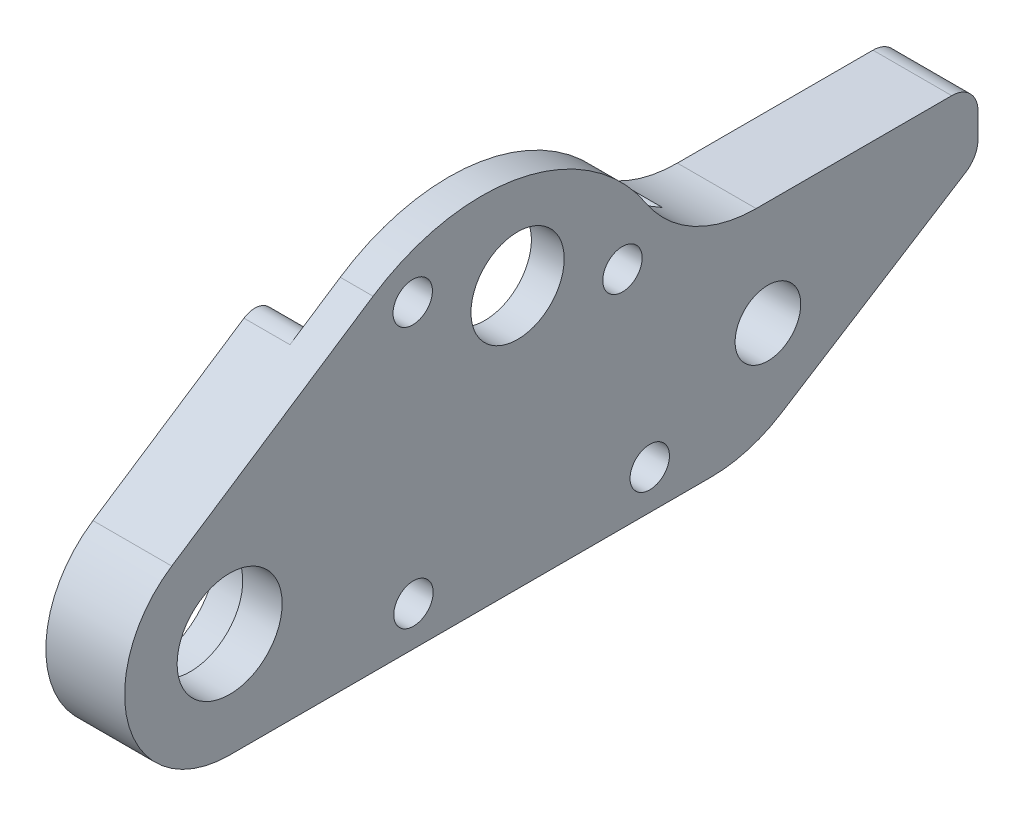
SolidWorks part; units mm, degrees
material "1060 Alloy"
ref_plane "Front Plane" through (0, 0, 0) normal (0, 0, 1) x (1, 0, 0)
ref_plane "Top Plane" through (0, 0, 0) normal (0, 1, 0) x (1, 0, 0)
ref_plane "Right Plane" through (0, 0, 0) normal (1, 0, 0) x (0, 0, -1)
sketch "Sketch27" plane through (0, 0, 0) normal (1, 0, 0) x (0, 0, -1)
  line L0 (4.5897, 48.6745) -> (19.925, 58.8075)
  line L1 (48.5644, 34) -> (66, 45)
  line L2 (66, 45) -> (66, 50)
  line L3 (38.9191, 51.0928) -> (22.9443, 56.9072) construction
  line L4 (66, 50) -> (49.1015, 50)
  line L6 (48.5644, 34) -> (9, 34)
  line L8 (0, 0) -> (60, 0) construction
  line L9 (0, 0) -> (0, 58) construction
  line L10 (0, 58) -> (60, 58) construction
  line L11 (60, 0) -> (60, 58) construction
  arc A0 (4.5897, 48.6745) -> (9, 34) centre (9, 42) ccw
  circle A1 centre (30.9317, 54) radius 12.5 construction
  arc A2 (40.7386, 54.5171) -> (19.925, 58.8075) centre (28.1943, 46.2928) ccw
  circle A3 centre (30.9317, 54) radius 3.55
  circle A4 centre (50, 42) radius 6 construction
  circle A5 centre (9, 42) radius 4
  circle A6 centre (50, 42) radius 2.5
  circle A7 centre (38.9191, 51.0928) radius 1.5
  circle A8 centre (22.9443, 56.9072) radius 1.5
  circle A9 centre (38.9191, 51.0928) radius 3.25 construction
  circle A10 centre (22.9443, 56.9072) radius 3.25 construction
  arc A12 (49.1015, 50) -> (40.7386, 54.5171) centre (49.1015, 60) cw
  dimension "D9" = 12
  dimension "D10" = 5
  dimension "D11" = 15
  dimension "D12" = 8
  dimension "D13" = 8
  dimension "D14" = 5
  dimension "D15" = 25
  dimension "D6" = 25
  dimension "D17" = 7.1
  dimension "D16" = 3
  dimension "D19" = 6.5
  dimension "D20" = 10
  dimension "D1" = 60
  dimension "D2" = 58
  dimension "D3" = 42
  dimension "D4" = 9
  dimension "D5" = 42
  dimension "D7" = 50
  dimension "D8" = 12
  dimension "D18" = 8.5
  dimension "D21" = 20
  dimension "D22" = 16
  dimension "D23" = 8
extrude "Boss-Extrude1" add sketch "Sketch27" along normal blind 6
sketch "Sketch47" plane through (0, 0, 0) normal (-1, 0, 0) x (0, 0, 1)
  circle A0 centre (-9, 42) radius 4.99
  dimension "D1" = 9.98
extrude "Cut-Extrude8" cut sketch "Sketch47" against normal blind 3
sketch "Sketch48" plane through (0, 0, 0) normal (-1, 0, 0) x (0, 0, 1)
  line L1 (-19.925, 58.8075) -> (-4.5897, 48.6745) construction
  line L2 (-45.3224, 50.7416) -> (-29.8529, 65.3675)
  line L4 (-29.8529, 65.3675) -> (-16.0921, 56.2749)
  arc A0 (-42.8655, 50.1159) -> (-18.415, 54.9141) centre (-30.9317, 54) ccw
  arc A1 (-42.8655, 50.1159) -> (-45.3224, 50.7416) centre (-44.2919, 49.6516) ccw
  arc A2 (-18.415, 54.9141) -> (-16.0921, 56.2749) centre (-16.919, 55.0234) cw
  arc A3 (-49.1015, 50) -> (-40.7386, 54.5171) centre (-49.1015, 60) ccw construction
  arc A4 (-19.925, 58.8075) -> (-40.7386, 54.5171) centre (-28.1943, 46.2928) ccw construction
  dimension "D1" = 12.55
  dimension "D2" = 1.5
  dimension "D3" = 1.5
extrude "Cut-Extrude10" cut sketch "Sketch48" against normal blind 3.5
sketch "Sketch49" plane through (0, 0, 0) normal (-1, 0, 0) x (0, 0, 1)
  line L0 (-44, 34) -> (-20, 34)
  line L1 (-44, 34) -> (-44, 40)
  line L2 (-20, 34) -> (-20, 40)
  line L3 (-44, 40) -> (-20, 40)
  line L4 (-9, 34) -> (-48.5644, 34) construction
  circle A0 centre (-50, 42) radius 2.5 construction
  dimension "D1" = 6
  dimension "D2" = 24
  dimension "D3" = 6
extrude "Cut-Extrude11" cut sketch "Sketch49" against normal blind 3
sketch "Sketch50" plane through (0, 0, 0) normal (-1, 0, 0) x (0, 0, 1)
  line L0 (-20, 40) -> (-44, 40) construction
  line L1 (-44, 40) -> (-44, 34) construction
  line L2 (-20, 34) -> (-20, 40) construction
  circle A0 centre (-43, 39) radius 1.5
  circle A1 centre (-21, 39) radius 1.5
  dimension "D1" = 3
  dimension "D2" = 1
  dimension "D3" = 1
  dimension "D4" = 1
extrude "Cut-Extrude12" cut sketch "Sketch50" against normal up to surface (3 mm away) up to face at (3, 37, -32)
fillet "Fillet1" radius 3 4 edges at (1.5, 37.882, -44) (1.5, 37.882, -20) (1.5, 40, -22.118) (1.5, 40, -41.882)
sketch "Sketch51" plane through (3, 0, 0) normal (-1, 0, 0) x (0, 0, 1)
  line L0 (-44, 34) -> (-20, 34) construction
  line L1 (-44, 36.9384) -> (-44, 34) construction
  line L2 (-20, 34) -> (-20, 36.9384) construction
  circle A0 centre (-41, 37) radius 1.5
  circle A1 centre (-23, 37) radius 1.5
  dimension "D1" = 3
  dimension "D2" = 3
  dimension "D3" = 3
  dimension "D4" = 3
  dimension "D5" = 3
extrude "Cut-Extrude13" cut sketch "Sketch51" against normal up to next
fillet "Fillet2" radius 10 1 edges at (3, 34, -48.5644)
fillet "Fillet3" radius 2 2 edges at (3, 50, -66) (3, 45, -66)
